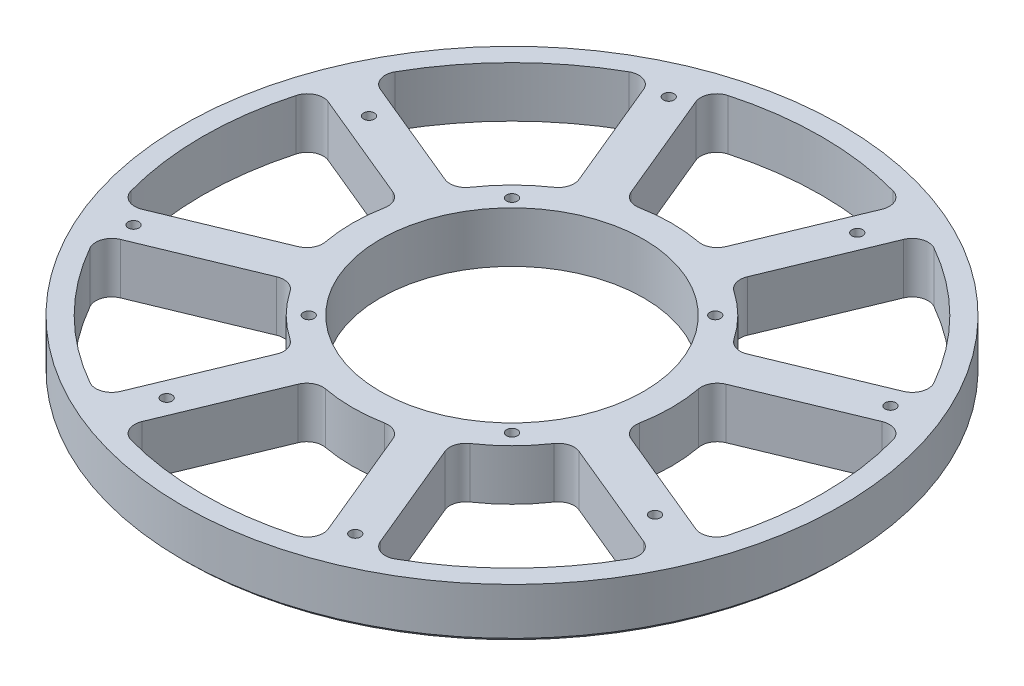
SolidWorks part; units mm, degrees
material "6061-T6 (SS)"
ref_plane "Front Plane" through (0, 0, 0) normal (0, 0, 1) x (1, 0, 0)
ref_plane "Top Plane" through (0, 0, 0) normal (0, 1, 0) x (1, 0, 0)
ref_plane "Right Plane" through (0, 0, 0) normal (1, 0, 0) x (0, 0, -1)
sketch "Sketch2" plane through (0, 0, 0) normal (1, 0, 0) x (0, 0, -1)
  line L0 (0, 0) -> (-82.55, 0)
  line L1 (-82.55, 0) -> (-82.55, 12.7)
  line L2 (-82.55, 12.7) -> (0, 12.7)
  line L5 (0, 12.7) -> (0, 0)
  dimension "D1" = 82.55
  dimension "D2" = 12.7
ref_axis "Axis1" through (0, -0.635, 0) along (0, 1, 0)
revolve "Revolve1" add sketch "Sketch2" angle 360 about axis through (0, -0.635, 0) along (0, 1, 0)
hole_wizard "#6-32 Tapped Hole1" positions "Sketch6" profile "Sketch7" tap size "#6-32" standard "ANSI Inch" end condition through all
sketch "Sketch6" plane through (0, 12.7, 0) normal (0, 1, 0) x (1, 0, 0)
  line L0 (0, 0) -> (-53.438, 129.0108) construction
  line L2 (0, 0) -> (0, 109.0908) construction
  line L3 (0, 0) -> (-76.2663, 31.5905) construction
  line L4 (0, 0) -> (-68.4315, 68.4315) construction
  circle A0 centre (0, 0) radius 82.55 construction
  point P0 (-27.7637, 67.0275)
  point P18 (-61.1608, 25.3336)
  point P27 (-25.4558, 25.4558)
  dimension "D1" = 22.5
  dimension "D2" = 72.55
  dimension "D3" = 45
  dimension "D4" = 66.2
  dimension "D6" = 22.5
  dimension "D5" = 36
sketch "Sketch7" plane through (-27.7637, 12.7, -67.0275) normal (1, 0, 0) x (0, 0, 1)
  line L0 (0, 0) -> (0, 12.7)
  line L1 (0, 12.7) -> (1.3525, 12.7)
  line L2 (1.3525, 12.7) -> (1.3525, 0)
  line L5 (1.3525, 0) -> (0, 0)
  line L11 (0, -6.35) -> (0, 107.95) construction
  dimension "Thread Major Dia." = 2.7051
  dimension "Thru Tap Drill Depth" = 12.7
pattern_circular "CirPattern3" count 4 over 360 about axis through (0, -0.635, 0) along (0, 1, 0) of "#6-32 Tapped Hole1"
sketch "Sketch8" plane through (0, 12.7, 0) normal (0, 1, 0) x (1, 0, 0)
  line L4 (0, 0) -> (0, 93.9995) construction
  line L5 (0, 0) -> (113.8372, 0) construction
  line L6 (-10.5679, 38.5787) -> (-24.996, 73.4112)
  line L7 (10.5679, 38.5787) -> (24.996, 73.4112)
  line L8 (0, 0) -> (-27.7637, 67.0275) construction
  arc A0 (-10.5679, 38.5787) -> (10.5679, 38.5787) centre (0, 0) cw
  arc A1 (-24.996, 73.4112) -> (24.996, 73.4112) centre (0, 0) cw
  circle A2 centre (0, 0) radius 82.55 construction
  dimension "D1" = 40
  dimension "D2" = 5
  dimension "D3" = 5
extrude "Cut-Extrude1" cut sketch "Sketch8" against normal through all
fillet "Fillet1" radius 4 4 edges at (10.5679, 6.35, -38.5787) (24.996, 6.35, -73.4112) (-10.5679, 6.35, -38.5787) (-24.996, 6.35, -73.4112)
pattern_circular "CirPattern4" count 8 over 360 about axis through (0, -0.635, 0) along (0, 1, 0) of "Cut-Extrude1", "Fillet1"
chamfer "Chamfer2" distance 1 angle 45 1 edges at (0, 0, -82.55)
sketch "Sketch9" plane through (0, 12.7, 0) normal (0, 1, 0) x (1, 0, 0)
  circle A0 centre (0, 0) radius 33
  dimension "D1" = 66
extrude "Cut-Extrude2" cut sketch "Sketch9" against normal through all
equation "\"TubeDiameter\"= 6.500in"
equation "\"D1@Sketch2\"=\"TubeDiameter\"/2"
equation "\"D2@Sketch6\"=\"TubeDiameter\"/2-10mm"
